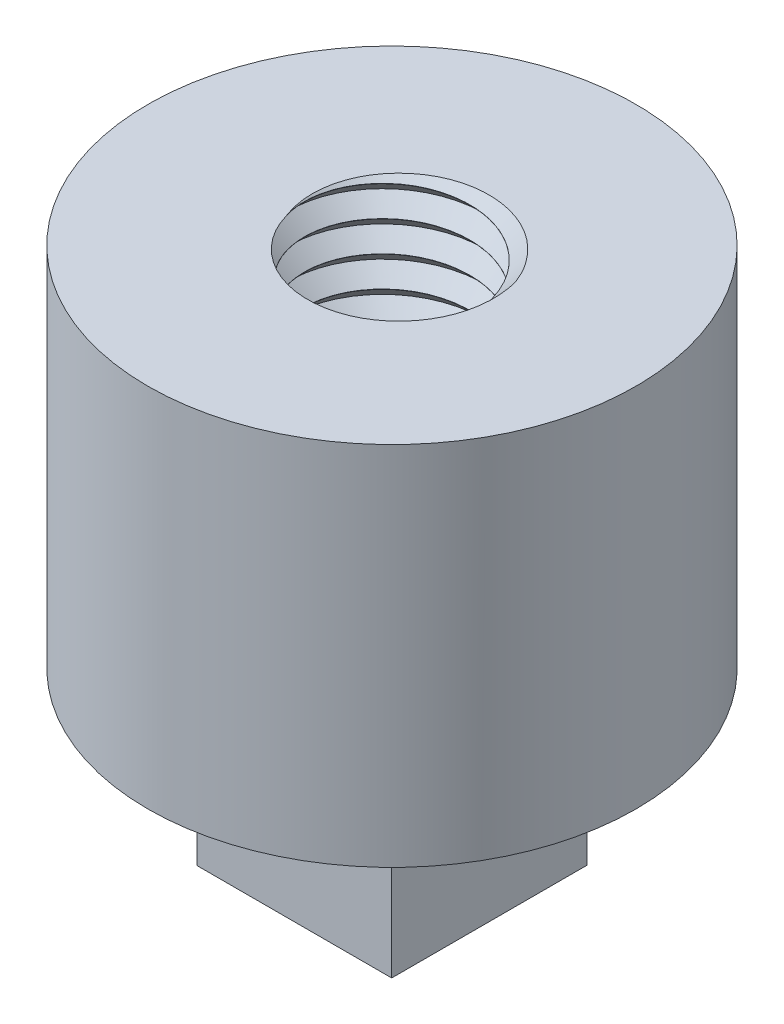
SolidWorks part; units mm, degrees
other "Markup1"
sketch "Sketch7" plane through (8, -40.1821, 8) normal (0.788, -0.5726, 0.226) x (0.2068, -0.0996, -0.9733)
other "Markup2"
sketch "Sketch8" plane through (10, -42.1821, -10) normal (0.2153, -0.7341, -0.6439) x (-0.8854, 0.1314, -0.4459)
material "7075-T6，板材(SS)"
ref_plane "前视基准面" through (0, 0, 0) normal (0, 0, 1) x (1, 0, 0)
ref_plane "上视基准面" through (0, 0, 0) normal (0, 1, 0) x (1, 0, 0)
ref_plane "右视基准面" through (0, 0, 0) normal (1, 0, 0) x (0, 0, -1)
sketch "草图1" plane through (0, 0, 0) normal (0, 0, 1) x (1, 0, 0)
  line L0 (0, 16.878) -> (0, -16.878) construction
  line L1 (0, 0) -> (3.4, 0) construction
  line L3 (3.4, 0) -> (10, 0)
  line L4 (3.4, 0) -> (3.4, -11)
  line L5 (3.4, -11) -> (10, -11)
  line L6 (10, 0) -> (10, -11)
  point P4 (0, 0)
  dimension "D1" = 3.4
  dimension "D2" = 10
  dimension "D3" = 11
revolve "旋转1" add sketch "草图1" angle 360 about L0
sketch "草图2" plane through (0, -11, 0) normal (0, -1, 0) x (1, 0, 0)
  circle A0 centre (0, 0) radius 3.4 construction
  circle A1 centre (0, 0) radius 3.4
curve "螺旋线/涡状线1" pitch 1.25 height 12.8125 radius 3.4 centre (0, -11, 0) axis (0, 1, 0) start towards (0, 0, -1)
sketch "草图3" plane through (0, 0, 0) normal (1, 0, 0) x (0, 0, -1)
  line L0 (3.4, -11.62) -> (3.4, -10.38)
  line L1 (3.4, -10.38) -> (4.025, -11)
  line L2 (-10, -11) -> (10, -11) construction
  line L3 (0, 0) -> (0, -13.2999) construction
  line L4 (-10, -11) -> (10, -11) construction
  line L5 (3.4, -11.62) -> (4.025, -11)
  spline S0 degree 3 poles (-996.1726, 15.4126) (-137.096, -13.3402) (13.9475, -12.0284) (2.4668, -10.8438) (1.335, -10.7656) (0, -10.6875) (-1.335, -10.6094) (-2.4668, -10.5313) (-3.223, -10.4531) (-3.4885, -10.375) (-3.223, -10.2969) (-2.4668, -10.2188) (-0.9577, -10.1146) (0.9577, -10.0104) (2.4668, -9.9063) (3.223, -9.8281) (3.4885, -9.75) (3.223, -9.6719) (2.4668, -9.5938) (0.9577, -9.4896) (-0.9577, -9.3854) (-2.4668, -9.2812) (-3.223, -9.2031) (-3.4885, -9.125) (-3.223, -9.0469) (-2.4668, -8.9687) (-0.9577, -8.8646) (0.9577, -8.7604) (2.4668, -8.6562) (3.223, -8.5781) (3.4885, -8.5) (3.223, -8.4219) (2.4668, -8.3437) (0.9577, -8.2396) (-0.9577, -8.1354) (-2.4668, -8.0312) (-3.223, -7.9531) (-3.4885, -7.875) (-3.223, -7.7969) (-2.4668, -7.7187) (-0.9577, -7.6146) (0.9577, -7.5104) (2.4668, -7.4062) (3.223, -7.3281) (3.4885, -7.25) (3.223, -7.1719) (2.4668, -7.0937) (0.9577, -6.9896) (-0.9577, -6.8854) (-2.4668, -6.7812) (-3.223, -6.7031) (-3.4885, -6.625) (-3.223, -6.5469) (-2.4668, -6.4687) (-0.9577, -6.3646) (0.9577, -6.2604) (2.4668, -6.1562) (3.223, -6.0781) (3.4885, -6) (3.223, -5.9219) (2.4668, -5.8437) (0.9577, -5.7396) (-0.9577, -5.6354) (-2.4668, -5.5312) (-3.223, -5.4531) (-3.4885, -5.375) (-3.223, -5.2969) (-2.4668, -5.2187) (-0.9577, -5.1146) (0.9577, -5.0104) (2.4668, -4.9062) (3.223, -4.8281) (3.4885, -4.75) (3.223, -4.6719) (2.4668, -4.5937) (0.9577, -4.4896) (-0.9577, -4.3854) (-2.4668, -4.2812) (-3.223, -4.2031) (-3.4885, -4.125) (-3.223, -4.0469) (-2.4668, -3.9687) (-0.9577, -3.8646) (0.9577, -3.7604) (2.4668, -3.6562) (3.223, -3.5781) (3.4885, -3.5) (3.223, -3.4219) (2.4668, -3.3437) (0.9577, -3.2396) (-0.9577, -3.1354) (-2.4668, -3.0312) (-3.223, -2.9531) (-3.4885, -2.875) (-3.223, -2.7969) (-2.4668, -2.7187) (-0.9577, -2.6146) (0.9577, -2.5104) (2.4668, -2.4062) (3.223, -2.3281) (3.4885, -2.25) (3.223, -2.1719) (2.4668, -2.0937) (0.9577, -1.9896) (-0.9577, -1.8854) (-2.4668, -1.7812) (-3.223, -1.7031) (-3.4885, -1.625) (-3.223, -1.5469) (-2.4668, -1.4687) (-0.9577, -1.3646) (0.9577, -1.2604) (2.4668, -1.1562) (3.223, -1.0781) (3.4885, -1) (3.223, -0.9219) (2.4668, -0.8437) (0.9577, -0.7396) (-0.9577, -0.6354) (-2.4668, -0.5312) (-3.223, -0.4531) (-3.4885, -0.375) (-3.223, -0.2969) (-2.4668, -0.2187) (-0.9577, -0.1146) (0.9577, -0.0104) (2.4668, 0.0938) (3.223, 0.1719) (3.4885, 0.25) (3.223, 0.3281) (2.4668, 0.4063) (0.9577, 0.5104) (-0.9577, 0.6146) (-2.4668, 0.7188) (-3.223, 0.7969) (-3.4885, 0.875) (-3.223, 0.9531) (-2.4668, 1.0313) (-0.9577, 1.1354) (0.9577, 1.2396) (2.4668, 1.3438) (3.223, 1.4219) (3.4885, 1.5) (3.2231, 1.5781) (2.4664, 1.6563) (-9.7756, 2.5015) (-56.5284, 3.3973) (999.7956, -6.0316) knots -0.259424 -0.259424 -0.259424 -0.259424 0.006098 0.012195 0.018293 0.02439 0.030488 0.036585 0.042683 0.04878 0.054878 0.060976 0.067073 0.079268 0.085366 0.091463 0.097561 0.103659 0.109756 0.115854 0.128049 0.134146 0.140244 0.146341 0.152439 0.158537 0.164634 0.176829 0.182927 0.189024 0.195122 0.20122 0.207317 0.213415 0.22561 0.231707 0.237805 0.243902 0.25 0.256098 0.262195 0.27439 0.280488 0.286585 0.292683 0.29878 0.304878 0.310976 0.323171 0.329268 0.335366 0.341463 0.347561 0.353659 0.359756 0.371951 0.378049 0.384146 0.390244 0.396341 0.402439 0.408537 0.420732 0.426829 0.432927 0.439024 0.445122 0.45122 0.457317 0.469512 0.47561 0.481707 0.487805 0.493902 0.5 0.506098 0.518293 0.52439 0.530488 0.536585 0.542683 0.54878 0.554878 0.567073 0.573171 0.579268 0.585366 0.591463 0.597561 0.603659 0.615854 0.621951 0.628049 0.634146 0.640244 0.646341 0.652439 0.664634 0.670732 0.676829 0.682927 0.689024 0.695122 0.70122 0.713415 0.719512 0.72561 0.731707 0.737805 0.743902 0.75 0.762195 0.768293 0.77439 0.780488 0.786585 0.792683 0.79878 0.810976 0.817073 0.823171 0.829268 0.835366 0.841463 0.847561 0.859756 0.865854 0.871951 0.878049 0.884146 0.890244 0.896341 0.908537 0.914634 0.920732 0.926829 0.932927 0.939024 0.945122 0.957317 0.963415 0.969512 0.97561 0.981707 0.987805 0.993902 1.179862 1.179862 1.179862 1.179862 only from (3.4, -11) to (0, 1.8125) construction
  spline S1 degree 3 poles (3.4, -11) (3.4, -10.9741) (3.223, -10.9218) (2.4668, -10.8438) (1.335, -10.7656) (0, -10.6875) (-1.335, -10.6094) (-2.4668, -10.5313) (-3.223, -10.4531) (-3.4885, -10.375) (-3.223, -10.2969) (-2.4668, -10.2188) (-0.9577, -10.1146) (0.9577, -10.0104) (2.4668, -9.9063) (3.223, -9.8281) (3.4885, -9.75) (3.223, -9.6719) (2.4668, -9.5938) (0.9577, -9.4896) (-0.9577, -9.3854) (-2.4668, -9.2812) (-3.223, -9.2031) (-3.4885, -9.125) (-3.223, -9.0469) (-2.4668, -8.9687) (-0.9577, -8.8646) (0.9577, -8.7604) (2.4668, -8.6562) (3.223, -8.5781) (3.4885, -8.5) (3.223, -8.4219) (2.4668, -8.3437) (0.9577, -8.2396) (-0.9577, -8.1354) (-2.4668, -8.0312) (-3.223, -7.9531) (-3.4885, -7.875) (-3.223, -7.7969) (-2.4668, -7.7187) (-0.9577, -7.6146) (0.9577, -7.5104) (2.4668, -7.4062) (3.223, -7.3281) (3.4885, -7.25) (3.223, -7.1719) (2.4668, -7.0937) (0.9577, -6.9896) (-0.9577, -6.8854) (-2.4668, -6.7812) (-3.223, -6.7031) (-3.4885, -6.625) (-3.223, -6.5469) (-2.4668, -6.4687) (-0.9577, -6.3646) (0.9577, -6.2604) (2.4668, -6.1562) (3.223, -6.0781) (3.4885, -6) (3.223, -5.9219) (2.4668, -5.8437) (0.9577, -5.7396) (-0.9577, -5.6354) (-2.4668, -5.5312) (-3.223, -5.4531) (-3.4885, -5.375) (-3.223, -5.2969) (-2.4668, -5.2187) (-0.9577, -5.1146) (0.9577, -5.0104) (2.4668, -4.9062) (3.223, -4.8281) (3.4885, -4.75) (3.223, -4.6719) (2.4668, -4.5937) (0.9577, -4.4896) (-0.9577, -4.3854) (-2.4668, -4.2812) (-3.223, -4.2031) (-3.4885, -4.125) (-3.223, -4.0469) (-2.4668, -3.9687) (-0.9577, -3.8646) (0.9577, -3.7604) (2.4668, -3.6562) (3.223, -3.5781) (3.4885, -3.5) (3.223, -3.4219) (2.4668, -3.3437) (0.9577, -3.2396) (-0.9577, -3.1354) (-2.4668, -3.0312) (-3.223, -2.9531) (-3.4885, -2.875) (-3.223, -2.7969) (-2.4668, -2.7187) (-0.9577, -2.6146) (0.9577, -2.5104) (2.4668, -2.4062) (3.223, -2.3281) (3.4885, -2.25) (3.223, -2.1719) (2.4668, -2.0937) (0.9577, -1.9896) (-0.9577, -1.8854) (-2.4668, -1.7812) (-3.223, -1.7031) (-3.4885, -1.625) (-3.223, -1.5469) (-2.4668, -1.4687) (-0.9577, -1.3646) (0.9577, -1.2604) (2.4668, -1.1562) (3.223, -1.0781) (3.4885, -1) (3.223, -0.9219) (2.4668, -0.8437) (0.9577, -0.7396) (-0.9577, -0.6354) (-2.4668, -0.5312) (-3.223, -0.4531) (-3.4885, -0.375) (-3.223, -0.2969) (-2.4668, -0.2187) (-0.9577, -0.1146) (0.9577, -0.0104) (2.4668, 0.0938) (3.223, 0.1719) (3.4885, 0.25) (3.223, 0.3281) (2.4668, 0.4063) (0.9577, 0.5104) (-0.9577, 0.6146) (-2.4668, 0.7188) (-3.223, 0.7969) (-3.4885, 0.875) (-3.223, 0.9531) (-2.4668, 1.0313) (-0.9577, 1.1354) (0.9577, 1.2396) (2.4668, 1.3438) (3.223, 1.4219) (3.4885, 1.5) (3.2231, 1.5781) (2.4664, 1.6563) (1.3363, 1.7343) (0.4422, 1.7866) (0, 1.8125) knots 0 0 0 0 0.006098 0.012195 0.018293 0.02439 0.030488 0.036585 0.042683 0.04878 0.054878 0.060976 0.067073 0.079268 0.085366 0.091463 0.097561 0.103659 0.109756 0.115854 0.128049 0.134146 0.140244 0.146341 0.152439 0.158537 0.164634 0.176829 0.182927 0.189024 0.195122 0.20122 0.207317 0.213415 0.22561 0.231707 0.237805 0.243902 0.25 0.256098 0.262195 0.27439 0.280488 0.286585 0.292683 0.29878 0.304878 0.310976 0.323171 0.329268 0.335366 0.341463 0.347561 0.353659 0.359756 0.371951 0.378049 0.384146 0.390244 0.396341 0.402439 0.408537 0.420732 0.426829 0.432927 0.439024 0.445122 0.45122 0.457317 0.469512 0.47561 0.481707 0.487805 0.493902 0.5 0.506098 0.518293 0.52439 0.530488 0.536585 0.542683 0.54878 0.554878 0.567073 0.573171 0.579268 0.585366 0.591463 0.597561 0.603659 0.615854 0.621951 0.628049 0.634146 0.640244 0.646341 0.652439 0.664634 0.670732 0.676829 0.682927 0.689024 0.695122 0.70122 0.713415 0.719512 0.72561 0.731707 0.737805 0.743902 0.75 0.762195 0.768293 0.77439 0.780488 0.786585 0.792683 0.79878 0.810976 0.817073 0.823171 0.829268 0.835366 0.841463 0.847561 0.859756 0.865854 0.871951 0.878049 0.884146 0.890244 0.896341 0.908537 0.914634 0.920732 0.926829 0.932927 0.939024 0.945122 0.957317 0.963415 0.969512 0.97561 0.981707 0.987805 0.993902 1 1 1 1 construction
  dimension "D1" = 4.025
  dimension "D2" = 0.62
sweep "切除-扫描1" cut profiles "草图3" path "螺旋线/涡状线1" align with end faces yes
sketch "草图4" plane through (0, 0, 0) normal (0, 0, 1) x (1, 0, 0)
  line L0 (-10, -11) -> (10, -11) construction
  line L1 (-10, -11) -> (10, -11) construction
  line L2 (0, 0) -> (0, -14.1821) construction
  line L3 (0, -13.3238) -> (4.025, -11)
  line L4 (4.025, -11) -> (10, -11)
  line L10 (0, -13.3238) -> (0, -14.1821)
  line L14 (10, -11) -> (10, -14.1821)
  line L15 (10, -14.1821) -> (0, -14.1821)
  dimension "D1" = 4.025
  dimension "D2" = 60
revolve "旋转2" add sketch "草图4" angle 360 about L2
sketch "Sketch9" plane through (0, -14.1821, 0) normal (0, -1, 0) x (1, 0, 0)
  circle A1 centre (0, 0) radius 10
  circle A2 centre (0, 0) radius 10
  dimension "D1" = 0
extrude "Boss-Extrude2" add sketch "Sketch9" along normal blind 0.82
sketch "草图5" plane through (0, -15.0021, 0) normal (0, -1, 0) x (1, 0, 0)
  line L1 (-3.9897, 4) -> (3.9897, 4)
  line L2 (-3.9897, 4) -> (-3.9897, -4)
  line L3 (-3.9897, -4) -> (3.9897, -4)
  line L4 (3.9897, 4) -> (3.9897, -4)
  line L5 (-3.9897, 4) -> (3.9897, -4) construction
  line L6 (-3.9897, -4) -> (3.9897, 4) construction
  point P0 (0, 0)
extrude "凸台-拉伸1" add sketch "草图5" along normal blind 7 contours L2 L1 L4 L3
